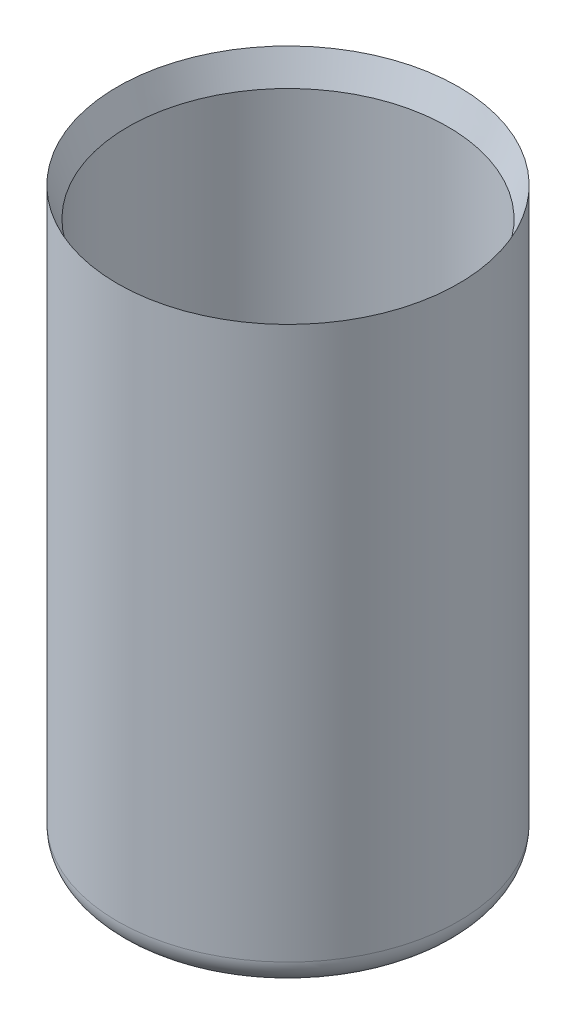
SolidWorks part; units mm, degrees
ref_plane "Front Plane" through (0, 0, 0) normal (0, 0, 1) x (1, 0, 0)
ref_plane "Top Plane" through (0, 0, 0) normal (0, 1, 0) x (1, 0, 0)
ref_plane "Right Plane" through (0, 0, 0) normal (1, 0, 0) x (0, 0, -1)
sketch "Sketch1" plane through (0, 0, 0) normal (0, 1, 0) x (1, 0, 0)
  circle A0 centre (0, 0) radius 30
  circle A1 centre (0, 0) radius 32
  dimension "D2" = 60
  dimension "D1" = 2
extrude "Boss-Extrude1" add sketch "Sketch1" against normal blind 10 contours A1 A0 | A0 region at (0, 0, 0) region at (-31.0949, 0, 0)
extrude "Boss-Extrude2" add sketch "Sketch1<3>" along normal blind 100
sketch "Sketch1<3>" plane through (0, 0, 0) normal (0, 1, 0) x (1, 0, 0) same geometry as "Sketch1"
fillet "Fillet1" radius 5 1 edges at (0, 0, 30)
fillet "Fillet2" radius 5 1 edges at (0, -10, 32)
sketch "Sketch2" plane through (0, -10, 0) normal (0, -1, 0) x (1, 0, 0)
  line L0 (-2.1651, 20.75) -> (-19.0526, -8.5)
  line L1 (-16.8875, -12.25) -> (16.8875, -12.25)
  line L2 (19.0526, -8.5) -> (2.1651, 20.75)
  line L3 (-10.6088, 6.125) -> (16.8875, -9.75) construction
  line L4 (16.8875, -9.75) -> (0, 19.5)
  line L5 (10.6088, 6.125) -> (-16.8875, -9.75) construction
  line L6 (0, 19.5) -> (-16.8875, -9.75)
  line L7 (0, -12.25) -> (0, 19.5) construction
  line L8 (-16.8875, -9.75) -> (16.8875, -9.75)
  line L9 (-2.5, 12) -> (-2.5, 0)
  line L10 (2.5, 0) -> (2.5, 12)
  arc A0 (2.1651, 20.75) -> (-2.1651, 20.75) centre (0, 19.5) ccw
  arc A1 (-19.0526, -8.5) -> (-16.8875, -12.25) centre (-16.8875, -9.75) ccw
  arc A2 (16.8875, -12.25) -> (19.0526, -8.5) centre (16.8875, -9.75) ccw
  circle A4 centre (0, 0) radius 22 construction
  circle A5 centre (0, 0) radius 27 construction
  arc A6 (0, 19.5) -> (0, 19.5) centre (0, 19.5) ccw
  arc A7 (-16.8875, -9.75) -> (-16.8875, -9.75) centre (-16.8875, -9.75) ccw
  arc A8 (16.8875, -9.75) -> (16.8875, -9.75) centre (16.8875, -9.75) ccw
  arc A9 (-2.5, 12) -> (2.5, 12) centre (0, 12) cw
  arc A10 (-2.5, 0) -> (2.5, 0) centre (0, 0) ccw
  circle A11 centre (0, -6) radius 2.5
  point P10 (0, 0)
  dimension "D1" = 2.5
  dimension "D2" = 5
  dimension "D4" = 5
  dimension "D5" = 12
  dimension "D6" = 6
  dimension "D3" = 2.5
extrude "Boss-Extrude3" add sketch "Sketch2" along normal blind 2 contours L1 A2 L2 A0 L0 A1 L8 L6 L4 | L9 A10 L10 A9 | A11 region at (0, -10, 21.4826) region at (0, -10, 6) region at (0, -10, -6)
chamfer "Chamfer1" distance 2.5 angle 70 1 edges at (0, 100, 30) first distance on face at (0, 100, 32)
equation "\"inner_diameter\"= 60mm"
equation "\"D2@Sketch1\"=\"inner_diameter\""
